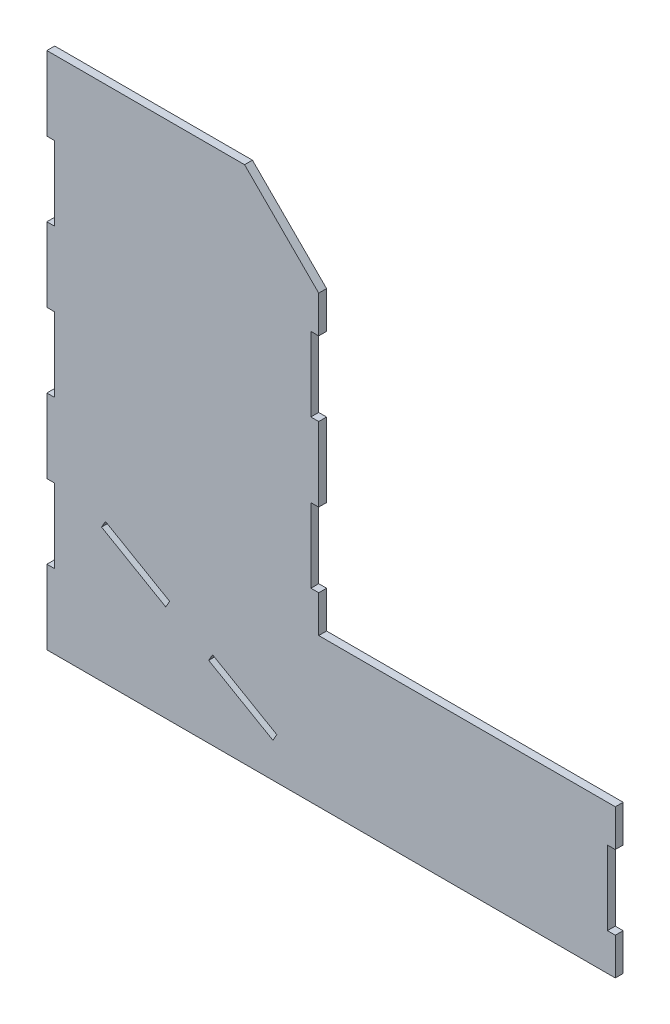
SolidWorks part; units mm, degrees
material "Maple"
ref_plane "Front Plane" through (0, 0, 0) normal (0, 0, 1) x (1, 0, 0)
ref_plane "Top Plane" through (0, 0, 0) normal (0, 1, 0) x (1, 0, 0)
ref_plane "Right Plane" through (0, 0, 0) normal (1, 0, 0) x (0, 0, -1)
sketch "Sketch1" plane through (0, 0, 0) normal (0, 0, 1) x (1, 0, 0)
  line L0 (-93.9149, 144.3977) -> (-93.9149, -65.6023)
  line L1 (-93.9149, -65.6023) -> (136.0851, -65.6023)
  line L2 (136.0851, -65.6023) -> (136.0851, -5.6023)
  line L3 (136.0851, -5.6023) -> (16.0851, -5.6023)
  line L4 (16.0851, -5.6023) -> (16.0851, 114.3977)
  line L5 (16.0851, 114.3977) -> (-13.9149, 144.3977)
  line L6 (-13.9149, 144.3977) -> (-93.9149, 144.3977)
  line L7 (-92.3274, 144.3977) -> (-92.3274, -65.6023) construction
  line L8 (-92.3274, 114.3977) -> (-92.3274, 84.3977)
  line L9 (-93.9149, 39.3977) -> (16.0851, 39.3977) construction
  line L10 (-92.3274, 24.3977) -> (-92.3274, 54.3977)
  line L11 (-92.3274, -35.6023) -> (-92.3274, -5.6023)
  line L12 (136.0851, -35.6023) -> (-93.9149, -35.6023) construction
  line L13 (14.4976, 114.3977) -> (14.4976, -5.6023) construction
  line L14 (14.4976, 99.3977) -> (14.4976, 69.3977)
  line L15 (14.4976, 54.3977) -> (0.0025, 54.3977) construction
  line L16 (14.4976, 9.3977) -> (14.4976, 39.3977)
  line L17 (134.4976, -5.6023) -> (134.4976, -65.6023) construction
  line L18 (134.4976, -20.6023) -> (134.4976, -50.6023)
  line L19 (-88.7399, 0.0934) -> (16.0851, -60.4273) construction
  line L20 (-70.9978, -10.1499) -> (-45.0171, -25.1499)
  line L21 (-36.3274, -30.1669) -> (-32.7271, -23.9311) construction
  line L22 (-1.657, -50.1839) -> (-27.6377, -35.1839)
  point P19 (-92.3274, 39.3977)
  dimension "D1" = 210
  dimension "D2" = 230
  dimension "D3" = 110
  dimension "D5" = 60
  dimension "D6" = 30
  dimension "D4" = 45
  dimension "D7" = 1.5875
  dimension "D8" = 0
  dimension "D9" = 0
  dimension "D10" = 30
  dimension "D11" = 30
  dimension "D12" = 30
  dimension "D13" = 30
  dimension "D14" = 30
  dimension "D15" = 1.5875
  dimension "D16" = 0
  dimension "D17" = 0
  dimension "D18" = 30
  dimension "D19" = 30
  dimension "D20" = 1.5875
  dimension "D21" = 0
  dimension "D22" = 0
  dimension "D23" = 30
  dimension "D24" = 30
  dimension "D25" = 3.5875
  dimension "D26" = 5.175
  dimension "D27" = 30
extrude "Boss-Extrude1" add sketch "Sketch1" along normal mid plane 3.175 contours L5 L6 L0 L1 L2 L3 L4 region at (-11.8546, 19.8751, 0)
extrude "Cut-Extrude-Thin1" cut sketch "Sketch1<3>" against normal through all both and the other way through all thin contours L8 | L10 | L11 | L14 | L16 | L18 | L20 | L22 thin type mid plane wall 3.18
sketch "Sketch1<3>" plane through (0, 0, 0) normal (0, 0, 1) x (1, 0, 0) same geometry as "Sketch1"
fillet "Fillet2" [suppressed] radius 4
equation "\"D7@Sketch1\"= \"lateral offset@tower.Assembly\""
equation "\"D8@Sketch1\" = \"vertical offset@tower.Assembly\""
equation "\"D9@Sketch1\"= \"vertical offset@tower.Assembly\""
equation "\"D12@Sketch1\"=\"D10@Sketch1\""
equation "\"D13@Sketch1\"=\"D10@Sketch1\""
equation "\"D11@Sketch1\"=\"D10@Sketch1\""
equation "\"D14@Sketch1\"=\"D10@Sketch1\""
equation "\"D1@Boss-Extrude1\" = \"T@tower.Assembly\""
equation "\"D15@Sketch1\"=\"D7@Sketch1\""
equation "\"D16@Sketch1\"=\"D8@Sketch1\""
equation "\"D17@Sketch1\"=\"D8@Sketch1\""
equation "\"D18@Sketch1\"=\"D10@Sketch1\""
equation "\"D19@Sketch1\"=\"D18@Sketch1\""
equation "\"D20@Sketch1\"=\"D7@Sketch1\""
equation "\"D21@Sketch1\"=\"D8@Sketch1\""
equation "\"D22@Sketch1\"=\"D8@Sketch1\""
equation "\"D23@Sketch1\"=\"D10@Sketch1\""
equation "\"D25@Sketch1\"=(\"T@tower.Assembly\"/2)+2"
equation "\"D26@Sketch1\"=\"T@tower.Assembly\"+2"
equation "\"D27@Sketch1\"=\"D10@Sketch1\""
